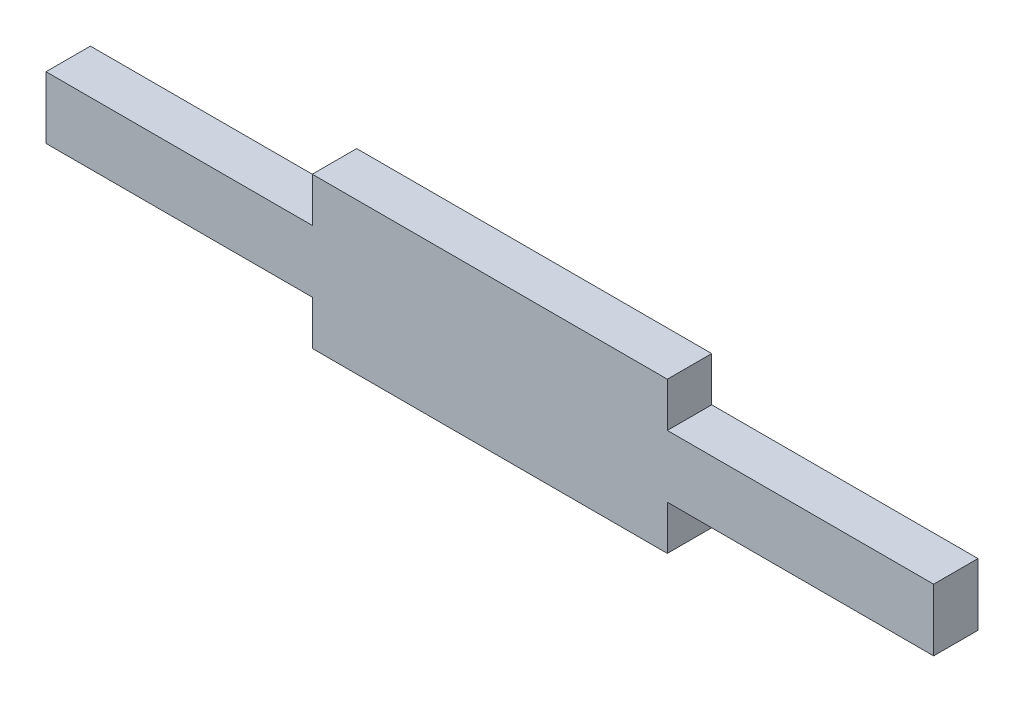
SolidWorks part; units mm, degrees
ref_plane "Front" through (0, 0, 0) normal (0, 0, 1) x (1, 0, 0)
ref_plane "Top" through (0, 0, 0) normal (0, 1, 0) x (1, 0, 0)
ref_plane "Right" through (0, 0, 0) normal (1, 0, 0) x (0, 0, -1)
sketch "Skizze1" plane through (0, 0, 0) normal (0, 0, 1) x (1, 0, 0)
  line L1 (0, 0) -> (100, 0)
  line L2 (0, 0) -> (0, -7)
  line L3 (0, -7) -> (100, -7)
  line L4 (100, 0) -> (100, -7)
  dimension "D1" = 7
  dimension "D2" = 100
extrude "Aufsatz-Linear austragen1" add sketch "Skizze1" along normal blind 5
sketch "Skizze2" plane through (0, 0, 0) normal (0, 1, 0) x (1, 0, 0)
  line L0 (50, 0) -> (50, -5) construction
  line L1 (100, 0) -> (0, 0) construction
  line L2 (100, -5) -> (0, -5) construction
  line L3 (70, 0) -> (30, 0)
  line L4 (30, 0) -> (30, -5)
  line L5 (30, -5) -> (70, -5)
  line L6 (70, 0) -> (70, -5)
  dimension "D1" = 40
extrude "Aufsatz-Linear austragen3" add sketch "Skizze2" along normal blind 5
ref_plane "Ebene1" through (0, -3.5, 0) normal (0, 1, 0) x (1, 0, 0)
mirror "Spiegeln1" about plane through (0, -3.5, 0) normal (0, 1, 0) of "Aufsatz-Linear austragen3"
